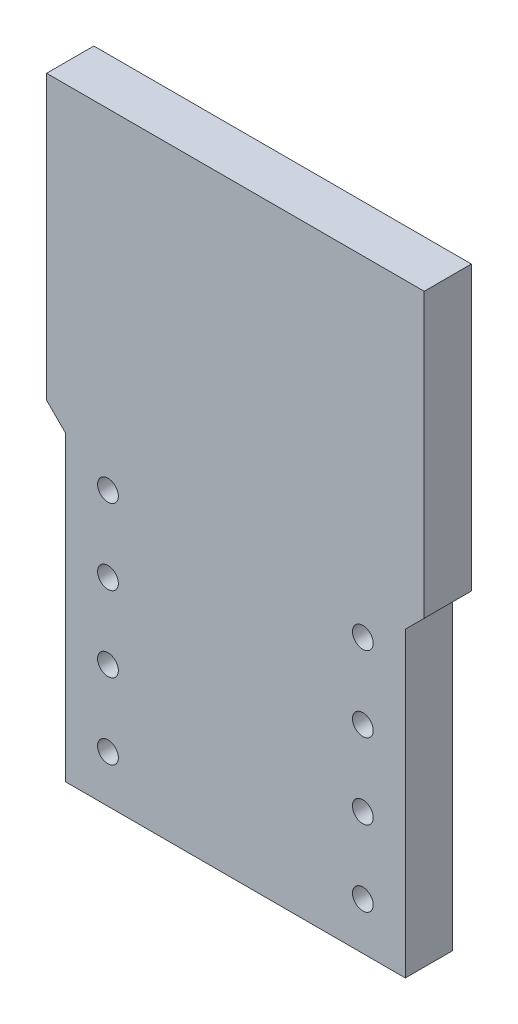
SolidWorks part; units mm, degrees
ref_plane "Alzado" through (0, 0, 0) normal (0, 0, 1) x (1, 0, 0)
ref_plane "Planta" through (0, 0, 0) normal (0, 1, 0) x (1, 0, 0)
ref_plane "Vista lateral" through (0, 0, 0) normal (1, 0, 0) x (0, 0, -1)
sketch "Croquis1" plane through (0, 0, 0) normal (0, 0, 1) x (1, 0, 0)
  line L0 (0, -15) -> (0, -49) construction
  line L1 (-20, 15) -> (20, 15)
  line L2 (-20, 15) -> (-20, -15)
  line L3 (-20, -15) -> (20, -15)
  line L4 (20, 15) -> (20, -15)
  line L5 (-20, 15) -> (20, -15) construction
  line L6 (-20, -15) -> (20, 15) construction
  line L7 (0, -20) -> (-13.5, -20) construction
  line L8 (18, -49) -> (-18, -49)
  line L9 (0, -49) -> (0, -15)
  line L10 (18, -15) -> (-18, -15)
  line L11 (-18, -49) -> (-18, -15)
  line L12 (-20, -15) -> (-18, -17)
  line L13 (20, -15) -> (18, -17)
  line L14 (18, -49) -> (18, -15)
  circle A0 centre (-13.5, -20) radius 1.1
  circle A1 centre (-13.5, -28) radius 1.1
  circle A2 centre (-13.5, -36) radius 1.1
  circle A3 centre (-13.5, -44) radius 1.1
  circle A4 centre (13.5, -20) radius 1.1
  circle A5 centre (13.5, -28) radius 1.1
  circle A6 centre (13.5, -36) radius 1.1
  circle A7 centre (13.5, -44) radius 1.1
  point P0 (0, 0)
  dimension "D5" = 2.2
  dimension "D1" = 40
  dimension "D2" = 30
  dimension "D3" = 18
  dimension "D4" = 13.5
  dimension "D7" = 34
  dimension "D8" = 5
  dimension "D9" = 45
  dimension "D6" = 4
extrude "Saliente-Extruir1" add sketch "Croquis1" along normal blind 5 contours L4 L1 L2 L3 | L11 L8 L9 L3 A3 A2 A1 A0 | L8 L14 L3 L9 A6 A4 A5 A7 | L3 L12 L11 | L14 L13 L3 region at (0, 0, 0) region at (-18.6667, -15.6667, 0) region at (18.6667, -15.6667, 0) region at (-8.8853, -32, 0) region at (8.8853, -32, 0)
